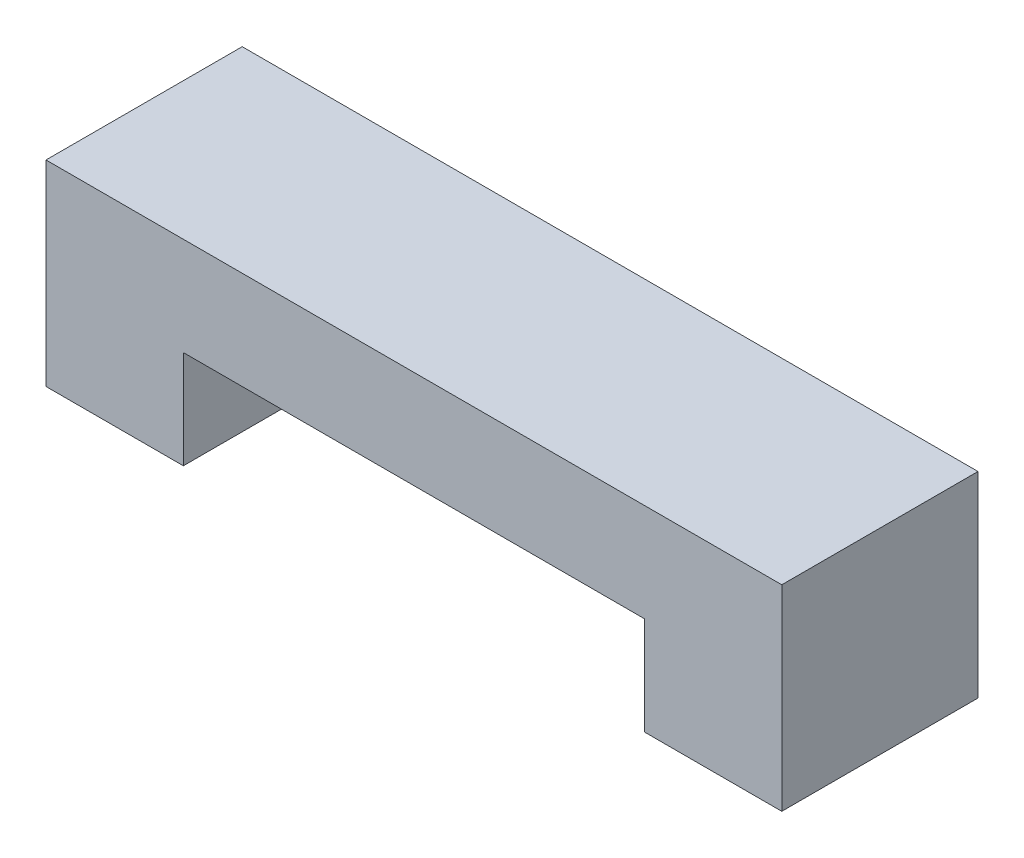
SolidWorks part; units mm, degrees
ref_plane "Front Plane" through (0, 0, 0) normal (0, 0, 1) x (1, 0, 0)
ref_plane "Top Plane" through (0, 0, 0) normal (0, 1, 0) x (1, 0, 0)
ref_plane "Right Plane" through (0, 0, 0) normal (1, 0, 0) x (0, 0, -1)
sketch "Croquis1" plane through (0, 0, 0) normal (0, 1, 0) x (1, 0, 0)
  line L0 (-18.75, -5) -> (-18.75, 5)
  line L1 (-18.75, -5) -> (18.75, -5)
  line L2 (-18.75, 5) -> (18.75, 5)
  line L3 (18.75, -5) -> (18.75, 5)
  line L4 (-18.75, -5) -> (18.75, 5) construction
  line L5 (-18.75, 5) -> (18.75, -5) construction
  line L6 (-11.75, 5) -> (-11.75, -5)
  line L7 (11.75, 5) -> (11.75, -5)
  circle A0 centre (-15, 0) radius 1.5
  circle A1 centre (15, 0) radius 1.5
  point P1 (0, 0)
  dimension "D3" = 3
  dimension "D4" = 3
  dimension "D1" = 37.5
  dimension "D2" = 10
  dimension "D5" = 15
  dimension "D6" = 15
  dimension "D7" = 5
  dimension "D8" = 7
  dimension "D9" = 7
  dimension "D10" = 5
extrude "Saliente-Extruir1" add sketch "Croquis1" along normal blind 5 contours L7 L2 L6 L1 | A0 | L6 L2 L0 L1 A0 | L2 L7 L1 L3 A1 | A1 region at (-18.6279, 0, 0) region at (0, 0, 0) region at (11.8721, 0, 0) region at (-15, 0, 0) region at (15, 0, 0)
extrude "Saliente-Extruir2" add sketch "Croquis1<3>" against normal blind 5 contours L6 L2 L0 L1 A0 | L2 L7 L1 L3 A1 region at (-18.6279, 0, 0) region at (11.8721, 0, 0)
sketch "Croquis1<3>" plane through (0, 0, 0) normal (0, 1, 0) x (1, 0, 0) same geometry as "Croquis1"
